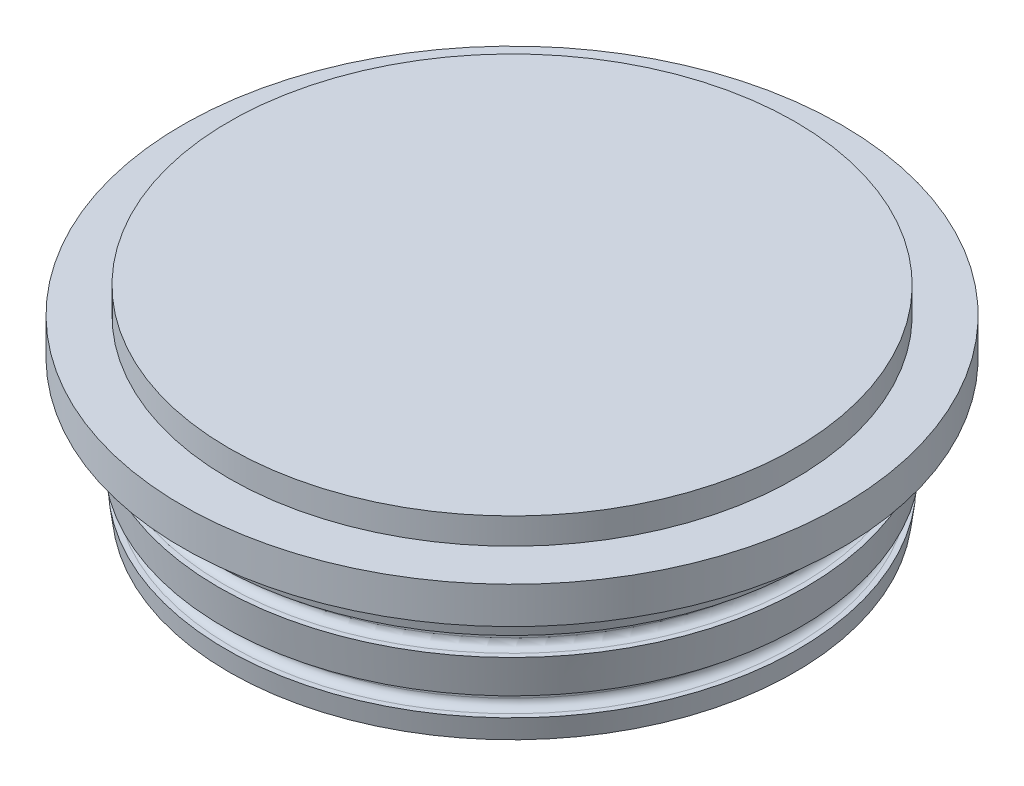
SolidWorks part; units mm, degrees
ref_plane "Plan de face" through (0, 0, 0) normal (0, 0, 1) x (1, 0, 0)
ref_plane "Plan de dessus" through (0, 0, 0) normal (0, 1, 0) x (1, 0, 0)
ref_plane "Plan de droite" through (0, 0, 0) normal (1, 0, 0) x (0, 0, -1)
sketch "Esquisse1" plane through (0, 0, 0) normal (0, 0, 1) x (1, 0, 0)
  line L0 (54, -32) -> (57.2913, -7) construction
  line L6 (0, 0) -> (0, 38.3863) construction
  line L7 (0, 0) -> (88.232, 0) construction
  line L18 (57.2913, -7) -> (62.9, -7)
  line L26 (54, -32) -> (54, -7) construction
  line L27 (54, -7) -> (57.2913, -7) construction
  line L29 (62.9, 0) -> (0, 0) construction
  line L30 (0, 0) -> (0, -6.5)
  line L31 (0, -6.5) -> (46, -6.5)
  line L32 (46, -6.5) -> (46, -32)
  line L33 (46, -32) -> (54, -32)
  line L34 (54, -32) -> (54.5266, -28)
  line L35 (54.5266, -28) -> (52.0532, -28)
  line L36 (52.0532, -28) -> (52.0532, -24)
  line L37 (52.0532, -24) -> (55.0532, -24)
  line L38 (55.0532, -24) -> (55.9748, -17)
  line L39 (55.9748, -17) -> (53.5014, -17)
  line L40 (53.5014, -17) -> (53.5014, -13)
  line L41 (53.5014, -13) -> (56.5014, -13)
  line L42 (56.5014, -13) -> (57.2913, -7)
  line L43 (62.9, -7) -> (62.9, 0)
  line L44 (62.9, 0) -> (54, 0)
  line L45 (54, 0) -> (54, 5)
  line L46 (54, 5) -> (0, 5)
  line L47 (0, 5) -> (0, 0)
  point P16 (65.9492, 0)
  dimension "D2" = 46
  dimension "D3" = 4
  dimension "D4" = 25
  dimension "D5" = 6.5
  dimension "D6" = 7.5
  dimension "D8" = 54
  dimension "D9" = 7
  dimension "D10" = 11
  dimension "D11" = 5
  dimension "D12" = 4
  dimension "D13" = 3
  dimension "D14" = 54
  dimension "D15" = 46
  dimension "D16" = 62.9
revolve "Révolution1" add sketch "Esquisse1" angle 360 about L6
fillet "Congé1" radius 1.5 4 edges at (0, -17, -53.5014) (0, -28, -52.0532) (0, -24, -52.0532) (0, -13, -53.5014)
fillet "Congé2" radius 10 1 edges at (0, -6.5, -46)
sketch "Esquisse2" plane through (0, -32, 0) normal (0, -1, 0) x (1, 0, 0)
  line L0 (0, 0) -> (54, 0) construction
  circle A0 centre (0, 0) radius 54 construction
  point P6 (50, 0)
  dimension "D1" = 50
hole_wizard "Trou taraudé M4x0.71" positions "Esquisse2" profile "Esquisse3" tap size "M4x0.7" standard "Ansi Metric"
sketch "Esquisse3" plane through (50, -32, 0) normal (1, 0, 0) x (0, 0, -1)
  line L0 (0, 0) -> (0, 18.5)
  line L1 (0, 18.5) -> (1.65, 18.5)
  line L2 (1.65, 18.5) -> (1.65, 0)
  line L5 (1.65, 0) -> (0, 0)
  line L10 (0, 18.5) -> (-1.65, 18.5) construction
  line L11 (0, -6.35) -> (0, 107.95) construction
  dimension "Diamètre du trou pour taraudage" = 3.3
  dimension "Profondeur du trou pour taraudage" = 18.5
  dimension "Angle de pointe" = 180
cosmetic thread "Filetage de perçage1" parameters "D1"=15, "D2"=4
pattern_circular "Répétition circulaire2" count 4 over 360 about axis through (0, -16.5, 0) along (0, 1, 0) of "Trou taraudé M4x0.71"
cosmetic thread "Filetage de perçage2" parameters "D1"=15, "D2"=4
cosmetic thread "Filetage de perçage3" parameters "D1"=15, "D2"=4
cosmetic thread "Filetage de perçage4" parameters "D1"=15, "D2"=4
equation "\"é\"=1"
